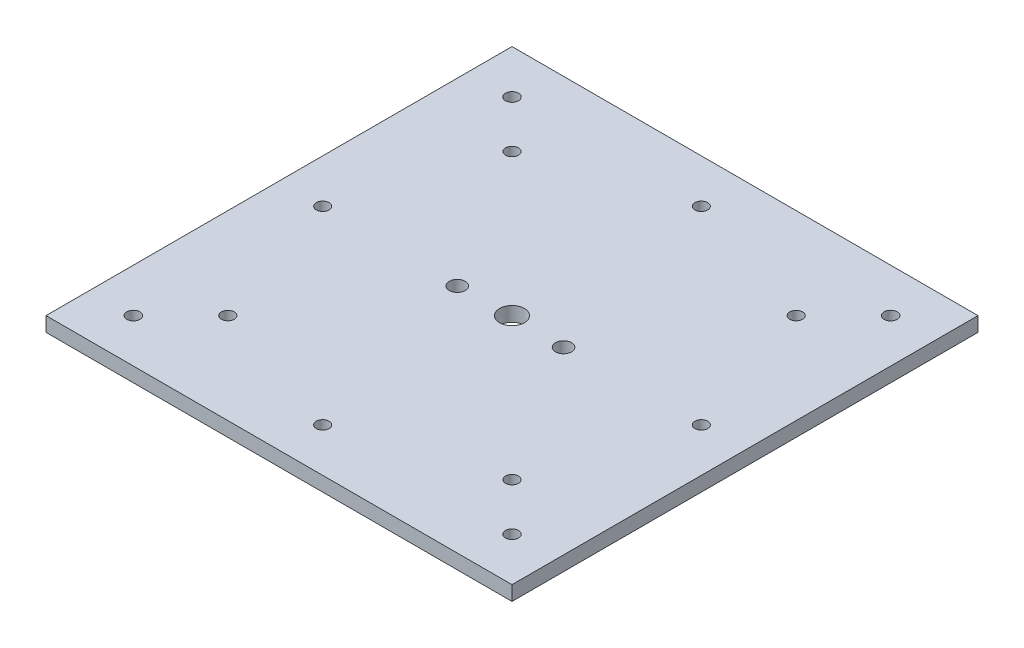
SolidWorks part; units mm, degrees
ref_plane "Front Plane" through (0, 0, 0) normal (0, 0, 1) x (1, 0, 0)
ref_plane "Top Plane" through (0, 0, 0) normal (0, 1, 0) x (1, 0, 0)
ref_plane "Right Plane" through (0, 0, 0) normal (1, 0, 0) x (0, 0, -1)
sketch "Sketch1" plane through (0, 0, 0) normal (0, 1, 0) x (1, 0, 0)
  line L0 (0, 80) -> (0, -80) construction
  line L1 (-80, 80) -> (80, 80)
  line L2 (-80, 80) -> (-80, -80)
  line L3 (-80, -80) -> (80, -80)
  line L4 (80, 80) -> (80, -80)
  line L5 (-80, 80) -> (80, -80) construction
  line L6 (-80, -80) -> (80, 80) construction
  circle A0 centre (0, 0) radius 69 construction
  circle A2 centre (48.7904, 48.7904) radius 2.2
  circle A4 centre (48.7904, -48.7904) radius 2.2
  circle A6 centre (-48.7904, -48.7904) radius 2.2
  circle A8 centre (-48.7904, 48.7904) radius 2.2
  circle A9 centre (0, 0) radius 4.25
  circle A10 centre (18.2724, -0.5716) radius 2.75
  circle A11 centre (-18.2276, -0.5716) radius 2.75
  circle A12 centre (0, 0) radius 65 construction
  circle A13 centre (0, 65) radius 2.2
  circle A14 centre (65, 0) radius 2.2
  circle A15 centre (0, -65) radius 2.2
  circle A16 centre (-65, 0) radius 2.2
  circle A18 centre (-65, 65) radius 2.25
  circle A19 centre (65, 65) radius 2.25
  circle A20 centre (65, -65) radius 2.25
  circle A21 centre (-65, -65) radius 2.25
  point P0 (0, 0)
  point P13 (0, 0)
  point P16 (0, 0)
  point P17 (0, 0)
  point P19 (0, 0)
  point P22 (0, 0)
  point P25 (0, 0)
  point P28 (0, 0)
  point P31 (0, 0)
  point P34 (0, 0)
  point P43 (0, 0)
  point P51 (93.538, 68.8172)
  dimension "D3" = 8
  dimension "D4" = 4
  dimension "D5" = 160
  dimension "D6" = 15
  dimension "D1" = 160
  dimension "D2" = 160
  dimension "D7" = 15
  dimension "D10" = 15
  dimension "D11" = 15
  dimension "D12" = 15
  dimension "D13" = 15
  dimension "D8" = 2
  dimension "D9" = 2
extrude "Boss-Extrude1" add sketch "Sketch1" along normal blind 5
